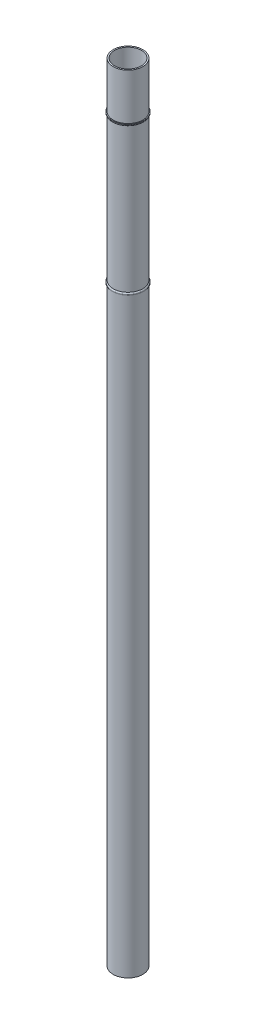
SolidWorks part; units mm, degrees
ref_plane "Front Plane" through (0, 0, 0) normal (0, 0, 1) x (1, 0, 0)
ref_plane "Top Plane" through (0, 0, 0) normal (0, 1, 0) x (1, 0, 0)
ref_plane "Right Plane" through (0, 0, 0) normal (1, 0, 0) x (0, 0, -1)
sketch "Sketch1" plane through (0, 0, 0) normal (0, 1, 0) x (1, 0, 0)
  circle A0 centre (0, 0) radius 16
  dimension "D1" = 32
extrude "Boss-Extrude1" add sketch "Sketch1" along normal blind 850
sketch "Sketch2" plane through (0, 850, 0) normal (0, 1, 0) x (1, 0, 0)
  circle A0 centre (0, 0) radius 14.5
  dimension "D1" = 29
extrude "Cut-Extrude1" cut sketch "Sketch2" against normal blind 848
ref_plane "Plane1" through (0, 800, 0) normal (0, 1, 0) x (1, 0, 0)
sketch "Sketch3" plane through (0, 800, 0) normal (0, 1, 0) x (1, 0, 0)
  circle A0 centre (0, 0) radius 17
  circle A1 centre (0, 0) radius 16
  dimension "D1" = 34
extrude "Boss-Extrude2" add sketch "Sketch3" against normal blind 2
fillet "Fillet1" radius 1.5 1 edges at (0, 798, 17)
ref_plane "Plane2" through (0, 640, 0) normal (0, 1, 0) x (1, 0, 0)
sketch "Sketch4" plane through (0, 640, 0) normal (0, 1, 0) x (1, 0, 0)
  circle A0 centre (0, 0) radius 17
  circle A1 centre (0, 0) radius 16
extrude "Boss-Extrude3" add sketch "Sketch4" along normal blind 2
fillet "Fillet2" radius 1.5 1 edges at (0, 642, 17)
